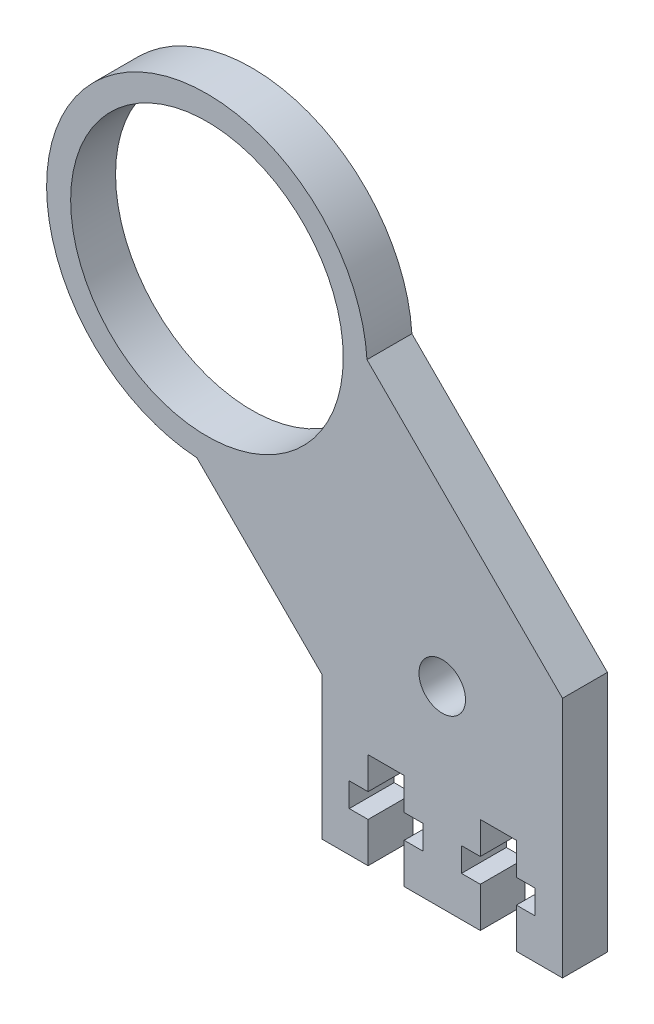
SolidWorks part; units mm, degrees
ref_plane "Front Plane" through (0, 0, 0) normal (0, 0, 1) x (1, 0, 0)
ref_plane "Top Plane" through (0, 0, 0) normal (0, 1, 0) x (1, 0, 0)
ref_plane "Right Plane" through (0, 0, 0) normal (1, 0, 0) x (0, 0, -1)
sketch "Sketch1" plane through (0, 0, 0) normal (0, 0, 1) x (1, 0, 0)
  line L0 (0, 0) -> (-29.3449, 29.3449) construction
  line L1 (0, 0) -> (0, 31.0325) construction
  line L2 (-15, -6.2132) -> (-15, -24)
  line L3 (-15, -24) -> (15, -24)
  line L4 (15, -24) -> (15, 6.2132)
  line L5 (0, 0) -> (0, -24) construction
  line L6 (15, 6.2132) -> (-9.3842, 30.5974)
  line L7 (-15, -6.2132) -> (-30.5974, 9.3842)
  line L8 (10.6066, 10.6066) -> (-18.7383, 39.9515) construction
  line L9 (-10.6066, -10.6066) -> (-39.9515, 18.7383) construction
  circle A0 centre (0, 0) radius 2.9
  arc A1 (-9.3842, 30.5974) -> (-30.5974, 9.3842) centre (-29.3449, 29.3449) ccw
  dimension "D1" = 5.8
  dimension "D3" = 40
  dimension "D2" = 41.5
  dimension "D4" = 45
  dimension "D5" = 24
  dimension "D6" = 30
  dimension "D7" = 15
  dimension "D8" = 15
extrude "Boss-Extrude1" add sketch "Sketch1" along normal blind 5.6
sketch "Sketch2" plane through (0, 0, 5.6) normal (0, 0, 1) x (1, 0, 0)
  circle A0 centre (-29.3449, 29.3449) radius 17
  dimension "D1" = 34
extrude "Cut-Extrude1" cut sketch "Sketch2" against normal through all
sketch "Sketch3" plane through (0, 0, 5.6) normal (0, 0, 1) x (1, 0, 0)
  line L0 (-15, -24) -> (15, -24) construction
  line L1 (-9.25, -24) -> (-4.75, -24)
  line L2 (-9.25, -24) -> (-9.25, -19)
  line L3 (-9.25, -12) -> (-4.75, -12)
  line L4 (-4.75, -24) -> (-4.75, -19)
  line L5 (0, 0) -> (0, -24) construction
  line L6 (-4.75, -16) -> (-2.4, -16)
  line L7 (-11.6, -16) -> (-9.25, -16)
  line L8 (-11.6, -16) -> (-11.6, -19)
  line L9 (-11.6, -19) -> (-9.25, -19)
  line L10 (-2.4, -16) -> (-2.4, -19)
  line L11 (-9.25, -16) -> (-9.25, -12)
  line L12 (-4.75, -19) -> (-2.4, -19)
  line L13 (-4.75, -16) -> (-4.75, -12)
  line L14 (4.75, -16) -> (4.75, -12)
  line L15 (4.75, -19) -> (2.4, -19)
  line L16 (9.25, -16) -> (9.25, -12)
  line L17 (2.4, -16) -> (2.4, -19)
  line L18 (11.6, -19) -> (9.25, -19)
  line L19 (11.6, -16) -> (11.6, -19)
  line L20 (11.6, -16) -> (9.25, -16)
  line L21 (4.75, -16) -> (2.4, -16)
  line L22 (4.75, -24) -> (4.75, -19)
  line L23 (9.25, -12) -> (4.75, -12)
  line L24 (9.25, -24) -> (9.25, -19)
  line L25 (9.25, -24) -> (4.75, -24)
  point P6 (-7, -12)
  point P18 (-10.425, -19)
  dimension "D1" = 4.5
  dimension "D2" = 7
  dimension "D3" = 12
  dimension "D4" = 9.2
  dimension "D5" = 3
  dimension "D6" = 5
extrude "Cut-Extrude2" cut sketch "Sketch3" against normal through all
equation "\"smallPulleyTeeth\"= 15"
equation "\"largePulleyTeeth\"= 30"
equation "\"eighthThick\"= 2.9mm"
equation "\"sixteenthThick\" = 1.7mm"
equation "\"wheelEighthThick\"=3.0mm"
equation "\"quarterThick\"=5.6mm"
equation "\"OD\" = 150mm"
equation "\"puckAngle\" = 60.5deg"
equation "\"puckDiam\" = 76.5mm"
equation "\"axlePress\" = 5.8mm"
equation "\"D1@Sketch1\"=\"axlePress\""
equation "\"D1@Boss-Extrude1\"=\"quarterThick\""
equation "\"press\" = 0.3mm"
equation "\"wheelClear\" = 0.3mm"
equation "\"10-32clear\" = 4.5mm"
equation "\"D1@Sketch3\"=\"10-32clear\""
